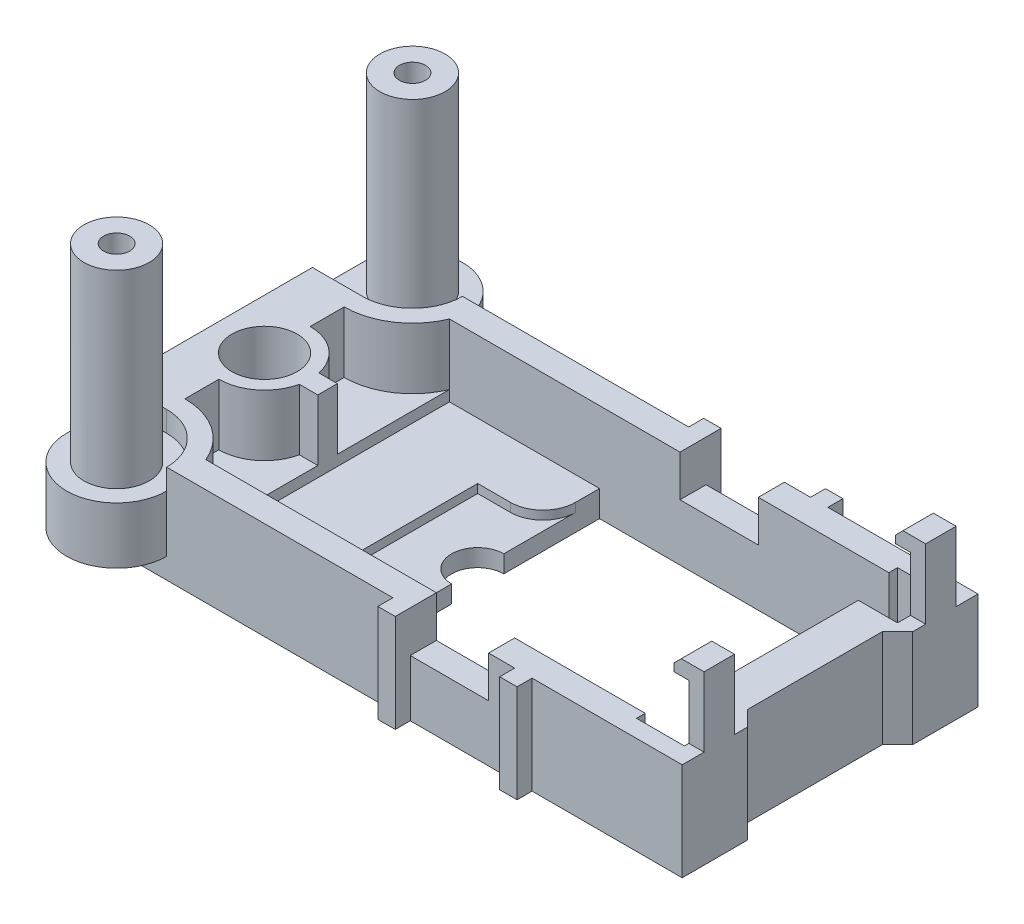
SolidWorks part; units mm, degrees
other "Camera1"
ref_plane "Front Plane" through (0, 0, 0) normal (0, 0, 1) x (1, 0, 0)
ref_plane "Top Plane" through (0, 0, 0) normal (0, 1, 0) x (1, 0, 0)
ref_plane "Right Plane" through (0, 0, 0) normal (1, 0, 0) x (0, 0, -1)
sketch "Sketch1" plane through (0, 0, 0) normal (0, 1, 0) x (1, 0, 0)
  line L1 (-17.9705, -8.636) -> (17.9705, -8.636)
  line L2 (-17.9705, -8.636) -> (-17.9705, 8.636)
  line L3 (-17.9705, 8.636) -> (17.9705, 8.636)
  line L4 (17.9705, -8.636) -> (17.9705, 8.636)
  line L5 (-17.9705, -8.636) -> (17.9705, 8.636) construction
  line L6 (-17.9705, 8.636) -> (17.9705, -8.636) construction
  point P0 (0, 0)
  dimension "D1" = 35.941
  dimension "D2" = 17.272
extrude "Boss-Extrude1" add sketch "Sketch1" along normal blind 5.715
sketch "Sketch2" plane through (0, 0, 8.636) normal (0, 0, 1) x (1, 0, 0)
  line L0 (-17.9705, 5.715) -> (17.9705, 5.715) construction
  line L1 (2.0955, 5.715) -> (2.0955, 0) construction
  line L2 (-17.9705, 0) -> (17.9705, 0) construction
  line L3 (2.0955, 3.302) -> (6.6675, 3.302)
  line L4 (6.6675, 3.302) -> (6.6675, 5.715)
  line L5 (2.0955, 3.302) -> (2.0955, 5.715)
  line L6 (2.0955, 5.715) -> (6.6675, 5.715)
  point P0 (6.6675, 5.715)
  point P1 (2.0955, 5.715)
  point P9 (2.0955, 3.302)
  dimension "D1" = 11.303
  dimension "D2" = 4.572
  dimension "D3" = 3.302
extrude "Cut-Extrude1" cut sketch "Sketch2" against normal through all
sketch "Sketch3" plane through (0, 5.715, 0) normal (0, 1, 0) x (1, 0, 0)
  line L0 (17.9705, -8.636) -> (17.9705, 8.636) construction
  line L1 (17.0815, 7.62) -> (17.0815, 4.826)
  line L2 (14.7955, 4.826) -> (14.7955, -4.826)
  line L3 (17.0815, -4.826) -> (17.0815, -7.62)
  line L4 (17.0815, 7.62) -> (14.2875, 7.62)
  line L5 (17.9705, 4.826) -> (17.0815, 3.937)
  line L6 (17.0815, 4.826) -> (14.7955, 4.826)
  line L7 (-17.9705, 8.636) -> (-17.9705, -8.636) construction
  line L8 (14.2875, 7.62) -> (14.2875, 7.112)
  line L9 (14.2875, 7.112) -> (-17.9705, 7.112)
  line L10 (17.0815, 3.937) -> (17.0815, -3.937)
  line L11 (-17.9705, 0) -> (17.9705, 0) construction
  line L12 (17.9705, -4.826) -> (17.0815, -3.937)
  line L13 (17.0815, -4.826) -> (14.7955, -4.826)
  line L14 (17.0815, -7.62) -> (17.0815, -4.826)
  line L15 (17.0815, -7.62) -> (14.2875, -7.62)
  line L16 (14.2875, -7.62) -> (14.2875, -7.112)
  line L17 (14.2875, -7.112) -> (-17.9705, -7.112)
  line L18 (2.0955, 8.636) -> (-17.9705, 8.636) construction
  line L19 (-11.3665, 7.112) -> (-11.3665, -7.112)
  line L20 (17.9705, 4.826) -> (17.9705, -4.826)
  line L21 (-2.6035, 7.112) -> (-2.6035, -7.112)
  point P0 (17.9705, 4.826)
  point P5 (-11.3665, 8.636)
  point P10 (17.9705, 7.62)
  point P11 (17.9705, -7.62)
  point P32 (-2.6035, 7.112)
  line M11 (2.0955, -8.636) -> (2.0955, 8.636)
  dimension "D1" = 3.81
  dimension "D2" = 3.175
  dimension "D3" = 1.016
  dimension "D4" = 1.016
  dimension "D5" = 29.337
  dimension "D6" = 45
  dimension "D7" = 8.763
extrude "Cut-Extrude2" cut sketch "Sketch3" against normal through all contours L21 L11 L9 M11 | L11 L2 L6 L1 L4 L8 L9 M11 | L11 L17 L16 L15 L3 L13 L2 M11 | L11 L21 L17 M11 | L11 L10 L12 L20 | L10 L11 L20 L5 region at (17.541, 5.715, -2.1983) region at (17.541, 5.715, 2.1983) region at (8.9553, 5.715, -3.7418) region at (8.9553, 5.715, 3.7418) region at (-0.254, 5.715, -3.556) region at (-0.254, 5.715, 3.556)
sketch "Sketch4" plane through (0, 5.715, 0) normal (0, 1, 0) x (1, 0, 0)
  line L0 (-2.6035, 7.112) -> (-11.3665, 7.112)
  line L1 (-2.6035, -7.112) -> (-11.3665, -7.112)
  line L2 (-11.3665, -7.112) -> (-11.3665, 7.112)
  line L3 (-2.6035, 7.112) -> (-2.6035, -7.112)
  dimension "D1" = 8.763
extrude "Cut-Extrude3" cut sketch "Sketch4" against normal blind 2.54
sketch "Sketch5" plane through (0, 3.175, 0) normal (0, 1, 0) x (1, 0, 0)
extrude "Cut-Extrude4" cut sketch "Sketch4<2>" against normal blind 4.191
sketch "Sketch4<2>" plane through (0, 5.715, 0) normal (0, 1, 0) x (1, 0, 0) same geometry as "Sketch4"
sketch "Sketch6" plane through (14.7955, 0, 0) normal (-1, 0, 0) x (0, 0, 1)
  line L0 (-4.826, 0) -> (-4.826, 5.715) construction
  line L1 (-4.826, 0.8763) -> (4.826, 0.8763)
  line L2 (4.826, 0) -> (4.826, 5.715) construction
  line L3 (4.826, 0.8763) -> (4.826, 0)
  line L4 (4.826, 0) -> (-4.826, 0)
  line L5 (-4.826, 0) -> (-4.826, 0.8763)
  point P0 (-4.826, 0.8763)
  dimension "D1" = 0.8763
extrude "Boss-Extrude2" add sketch "Sketch6" along normal blind 0.8763
sketch "Sketch7" plane through (0, 5.715, 0) normal (0, 1, 0) x (1, 0, 0)
  line L0 (17.0815, 0) -> (-17.9705, 0) construction
  line L1 (17.0815, 3.937) -> (17.0815, -3.937) construction
  line L2 (-17.9705, 8.636) -> (-17.9705, -8.636) construction
  line L3 (17.0815, 7.359) -> (17.0815, 5.581)
  line L4 (17.0815, 7.62) -> (17.0815, 4.826) construction
  line L5 (17.0815, 7.359) -> (17.9705, 7.359)
  line L6 (17.9705, 4.826) -> (17.9705, 8.636) construction
  line L7 (17.9705, 7.359) -> (17.9705, 5.581)
  line L8 (17.9705, 5.581) -> (17.0815, 5.581)
  line L9 (17.0815, -7.359) -> (17.0815, -5.581)
  line L10 (17.9705, -5.581) -> (17.0815, -5.581)
  line L11 (17.9705, -7.359) -> (17.9705, -5.581)
  line L12 (17.0815, -7.359) -> (17.9705, -7.359)
  point P11 (17.0815, 6.47)
  dimension "D1" = 1.778
extrude "Boss-Extrude3" add sketch "Sketch7" along normal blind 4.064 contours L9 L10 L11 L12 | L8 L3 L5 L7
sketch "Sketch9" plane through (17.0815, 0, 0) normal (-1, 0, 0) x (0, 0, 1)
  line L0 (-7.359, 9.779) -> (-7.359, 5.715) construction
  line L1 (-7.359, 8.9027) -> (-5.581, 8.9027)
  line L2 (-5.581, 9.779) -> (-5.581, 5.715) construction
  line L3 (-5.581, 8.9027) -> (-5.581, 9.779)
  line L4 (-5.581, 9.779) -> (-7.359, 9.779)
  line L5 (-7.359, 9.779) -> (-7.359, 8.9027)
  line L6 (5.581, 8.9027) -> (7.359, 8.9027)
  line L7 (5.581, 9.779) -> (5.581, 5.715) construction
  line L8 (7.359, 9.779) -> (7.359, 5.715) construction
  line L9 (7.359, 8.9027) -> (7.359, 9.779)
  line L10 (7.359, 9.779) -> (5.581, 9.779)
  line L11 (5.581, 9.779) -> (5.581, 8.9027)
  point P0 (-7.359, 8.9027)
  dimension "D1" = 0.8763
extrude "Boss-Extrude5" add sketch "Sketch9" along normal blind 0.8763
chamfer "Chamfer1" distance 0.4381 2 edges at (16.2052, 9.779, 6.47) (16.2052, 9.779, -6.47)
ref_plane "Plane1" through (0, 0, 0) normal (0, 0, 1) x (1, 0, 0)
sketch "Sketch11" plane through (0, 0, -8.636) normal (0, 0, -1) x (-1, 0, 0)
  line L0 (-2.0955, 5.715) -> (17.9705, 5.715) construction
  line L1 (-1.0795, 5.715) -> (-1.0795, 0)
  line L2 (-17.9705, 0) -> (17.9705, 0) construction
  line L3 (-1.0795, 5.715) -> (-2.0955, 5.715)
  line L4 (-2.0955, 5.715) -> (-2.0955, 0)
  line L5 (-2.0955, 0) -> (-1.0795, 0)
  line L6 (-17.9705, 5.715) -> (-6.6675, 5.715) construction
  line L7 (-9.2075, 5.715) -> (-9.2075, 0)
  line L8 (-9.2075, 0) -> (-8.1915, 0)
  line L9 (-8.1915, 0) -> (-8.1915, 5.715)
  line L10 (-8.1915, 5.715) -> (-9.2075, 5.715)
  point P0 (-1.0795, 5.715)
  point P9 (-8.1915, 5.715)
  point P11 (-9.2075, 5.715)
  dimension "D1" = 1.016
  dimension "D2" = 1.524
  dimension "D3" = 1.016
extrude "Boss-Extrude6" add sketch "Sketch11" along normal blind 0.8763
mirror "Mirror1" about plane through (0, 0, 0) normal (0, 0, 1) of "Boss-Extrude6"
sketch "Sketch12" plane through (0, 1.524, 0) normal (0, 1, 0) x (1, 0, 0)
  line L0 (-2.6035, 0) -> (-6.4135, 0) construction
  line L1 (-2.6035, -7.112) -> (-2.6035, 7.112) construction
  line L2 (-2.6613, 0) -> (2.6613, 0) construction
  line L3 (-6.4135, 3.81) -> (-6.4135, -3.81)
  line L4 (-6.4135, -3.81) -> (-4.5085, -3.81)
  line L5 (-2.6035, -5.715) -> (-2.6035, 5.715)
  line L6 (-4.5085, 3.81) -> (-6.4135, 3.81)
  line L7 (-2.6035, -5.715) -> (-2.6035, -7.112)
  line L8 (-2.6035, 5.715) -> (-2.6035, 7.112)
  arc A0 (-2.6035, 5.715) -> (-4.5085, 3.81) centre (-4.5085, 5.715) cw
  arc A1 (-2.6035, -5.715) -> (-4.5085, -3.81) centre (-4.5085, -5.715) ccw
  point P10 (-6.4135, 0)
  line M5 (-2.6035, -7.112) -> (-2.6035, 7.112)
  dimension "D3" = 1.905
  dimension "D1" = 3.81
  dimension "D2" = 7.62
extrude "Cut-Extrude5" cut sketch "Sketch12" against normal blind 0.508 contours L0 L3 L4 A1 M5 | L0 L5 A0 L6 L3 region at (-4.4332, 1.524, 2.0237) region at (-4.4332, 1.524, -2.0237)
sketch "Sketch13" plane through (0, 1.016, 0) normal (0, 1, 0) x (1, 0, 0)
  line L0 (-2.6035, -5.715) -> (-2.6035, 5.715) construction
  line L1 (-2.6035, -1.524) -> (-2.6035, 1.524)
  arc A0 (-2.6035, 1.524) -> (-2.6035, -1.524) centre (-2.6035, 0) ccw
  dimension "D1" = 1.524
extrude "Cut-Extrude6" cut sketch "Sketch13" against normal through all
sketch "Sketch20" plane through (0, 0, 8.636) normal (0, 0, 1) x (1, 0, 0)
  line L0 (-17.9705, 2.8575) -> (-12.1285, 2.8575) construction
  line L1 (-17.9705, 5.715) -> (-17.9705, 0) construction
  line L2 (-17.9705, 1.2065) -> (-17.9705, 4.5085)
  line L3 (-17.9705, 1.2065) -> (-12.1285, 1.2065)
  line L4 (-12.1285, 1.2065) -> (-12.1285, 4.5085)
  line L5 (-12.1285, 4.5085) -> (-17.9705, 4.5085)
  point P7 (-17.9705, 2.8575)
  dimension "D1" = 5.842
  dimension "D2" = 3.302
extrude "Boss-Extrude8" add sketch "Sketch20" along normal blind 4.318
mirror "Mirror5" about plane through (0, 0, 0) normal (0, 0, 1) of "Boss-Extrude8"
sketch "Sketch23" plane through (0, 5.715, 0) normal (0, 1, 0) x (1, 0, 0)
  line L5 (-12.1285, -8.636) -> (-17.9705, -8.636) construction
  line L6 (-15.0495, -5.715) -> (-17.9705, -5.715)
  line L7 (-17.9705, 8.636) -> (-17.9705, -8.636) construction
  line L8 (-12.1285, -8.636) -> (-17.9705, -8.636)
  line L9 (-17.9705, -8.636) -> (-17.9705, -5.715)
  arc A1 (-12.1285, -8.636) -> (-15.0495, -5.715) centre (-15.0495, -8.636) ccw
extrude "Cut-Extrude12" cut sketch "Sketch23" against normal blind 1.2065
mirror "Mirror8" about plane through (0, 0, 0) normal (0, 0, 1) of "Cut-Extrude12"
sketch "Sketch24" plane through (0, 4.5085, 0) normal (0, 1, 0) x (1, 0, 0)
  line L0 (-12.1285, -8.636) -> (-17.9705, -8.636) construction
  line L1 (-17.9705, -12.954) -> (-17.9705, -5.715) construction
sketch "Sketch25" plane through (0, 4.5085, 0) normal (0, 1, 0) x (1, 0, 0)
  line L0 (-12.1285, -8.636) -> (-17.9705, -8.636) construction
  line L1 (-12.1285, -8.636) -> (-12.1285, -12.954)
  line L2 (-12.1285, -12.954) -> (-17.9705, -12.954)
  line L3 (-17.9705, -12.954) -> (-17.9705, -8.636)
  arc A0 (-17.9705, -8.636) -> (-12.1285, -8.636) centre (-15.0495, -8.636) ccw
extrude "Cut-Extrude13" cut sketch "Sketch25" against normal through all
mirror "Mirror9" about plane through (0, 0, 0) normal (0, 0, 1) of "Cut-Extrude13"
sketch "Sketch26" plane through (0, 4.5085, 0) normal (0, 1, 0) x (1, 0, 0)
  line L0 (-12.1285, -8.636) -> (-17.9705, -8.636) construction
  circle A0 centre (-15.0495, -8.636) radius 1.905
  circle A1 centre (-15.0495, -8.636) radius 0.762
  dimension "D1" = 3.81
  dimension "D2" = 1.524
extrude "Boss-Extrude9" add sketch "Sketch26" along normal blind 11.049
mirror "Mirror10" about plane through (0, 0, 0) normal (0, 0, 1) of "Boss-Extrude9"
sketch "Sketch27" plane through (0, 5.715, 0) normal (0, 1, 0) x (1, 0, 0)
  line L0 (-11.3665, -0.5715) -> (-11.3665, 0.5715)
  line L1 (-17.9705, 5.715) -> (-17.9705, -5.715) construction
  line L2 (-2.6613, 0) -> (2.6613, 0) construction
  line L3 (-11.3665, -0.5715) -> (-12.4445, -0.5715)
  line L4 (-12.1285, -8.636) -> (-17.9705, -8.636) construction
  line L5 (-11.3665, 7.112) -> (-11.3665, -7.112) construction
  line L6 (-15.0495, -4.6501) -> (-15.0495, 4.6501) construction
  line L7 (-11.3665, 0) -> (-12.3825, 0) construction
  line L8 (-11.3665, 0.5715) -> (-12.4445, 0.5715)
  line L9 (-15.0495, -4.6501) -> (-15.0495, -2.667)
  line L10 (-15.0495, 4.6501) -> (-15.0495, 2.667)
  arc A0 (-11.3665, -7.112) -> (-15.0495, -4.6501) centre (-15.0495, -8.636) ccw
  arc A4 (-11.3665, 7.112) -> (-15.0495, 4.6501) centre (-15.0495, 8.636) cw
  circle A5 centre (-15.0495, 0) radius 1.905
  arc A6 (-15.0495, 2.667) -> (-15.0495, -2.667) centre (-15.0495, 0) cw
  point P6 (-11.3665, 0)
  point P14 (-17.9705, 0)
  point P18 (-15.0495, 2.667)
  line M16 (-11.3665, -7.112) -> (-11.3665, 7.112)
  dimension "D3" = 1.016
  dimension "D4" = 2.667
  dimension "D2" = 3.81
  dimension "D1" = 1.143
  dimension "D5" = 2.667
extrude "Cut-Extrude14" cut sketch "Sketch27" against normal blind 3.5687 contours L10 A6 L8 A4 M16 | L3 A6 L9 A0 M16 | A5 region at (-12.7876, 5.715, 3.4693) region at (-12.7876, 5.715, -3.4693)
sketch "Sketch29" plane through (0, 2.1463, 0) normal (0, 1, 0) x (1, 0, 0)
  circle A0 centre (-15.0495, 0) radius 0.762
  dimension "D1" = 1.524
extrude "Cut-Extrude15" cut sketch "Sketch29" against normal through all
